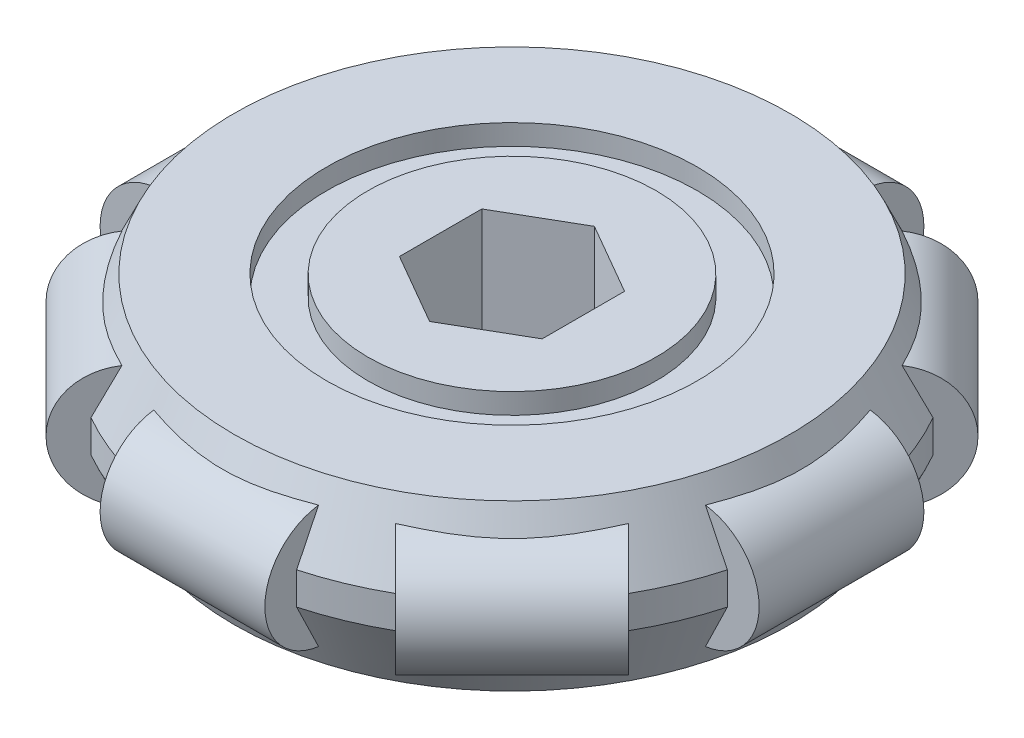
SolidWorks part; units mm, degrees
ref_plane "Front Plane" through (0, 0, 0) normal (0, 0, 1) x (1, 0, 0)
ref_plane "Top Plane" through (0, 0, 0) normal (0, 1, 0) x (1, 0, 0)
ref_plane "Right Plane" through (0, 0, 0) normal (1, 0, 0) x (0, 0, -1)
sketch "Sketch2" plane through (0, 0, 0) normal (0, 1, 0) x (1, 0, 0)
  circle A0 centre (0, 0) radius 23.8125
  dimension "D1" = 47.625
extrude "Boss-Extrude1" add sketch "Sketch2" along normal blind 6.35 and the other way blind 6.35
sketch "Sketch4" plane through (0, 0, 0) normal (1, 0, 0) x (0, 0, -1)
  line L0 (-25.4, 0) -> (0, 0) construction
  circle A0 centre (-20.6375, 0) radius 4.7625
  dimension "D2" = 9.525
  dimension "D1" = 25.4
extrude "Boss-Extrude2" add sketch "Sketch4" along normal blind 6.35 and the other way blind 6.35
chamfer "Chamfer1" distance 2.3813 angle 65 2 edges at (0, 6.35, 23.8125) (0, -6.35, 23.8125) first distance on face at (0, 6.35, 23.8125) first distance on face at (0, -6.35, 23.8125)
pattern_circular "CirPattern1" count 8 every 45 about axis through (0, 6.35, 0) along (0, 1, 0) of "Boss-Extrude2"
sketch "Sketch6" plane through (0, 6.35, 0) normal (0, 1, 0) x (1, 0, 0)
  line L1 (0, 6.3509) -> (-5.5, 3.1754)
  line L2 (-5.5, 3.1754) -> (-5.5, -3.1754)
  line L3 (-5.5, -3.1754) -> (0, -6.3509)
  line L4 (0, -6.3509) -> (5.5, -3.1754)
  line L5 (5.5, -3.1754) -> (5.5, 3.1754)
  line L6 (5.5, 3.1754) -> (0, 6.3509)
  circle A0 centre (0, 0) radius 5.5 construction
  dimension "D1" = 11
extrude "Cut-Extrude1" cut sketch "Sketch6" against normal through all contours L3 L4 L5 L6 L1 L2
sketch "Sketch7" plane through (0, 6.35, 0) normal (0, 1, 0) x (1, 0, 0)
  circle A0 centre (0, 0) radius 14.2875
  circle A1 centre (0, 0) radius 11.1125
  dimension "D1" = 22.225
  dimension "D2" = 3.175
extrude "Cut-Extrude2" cut sketch "Sketch7" against normal blind 1.5875
mirror "Mirror1" about plane through (0, 0, 0) normal (0, 1, 0) of "Cut-Extrude2"
